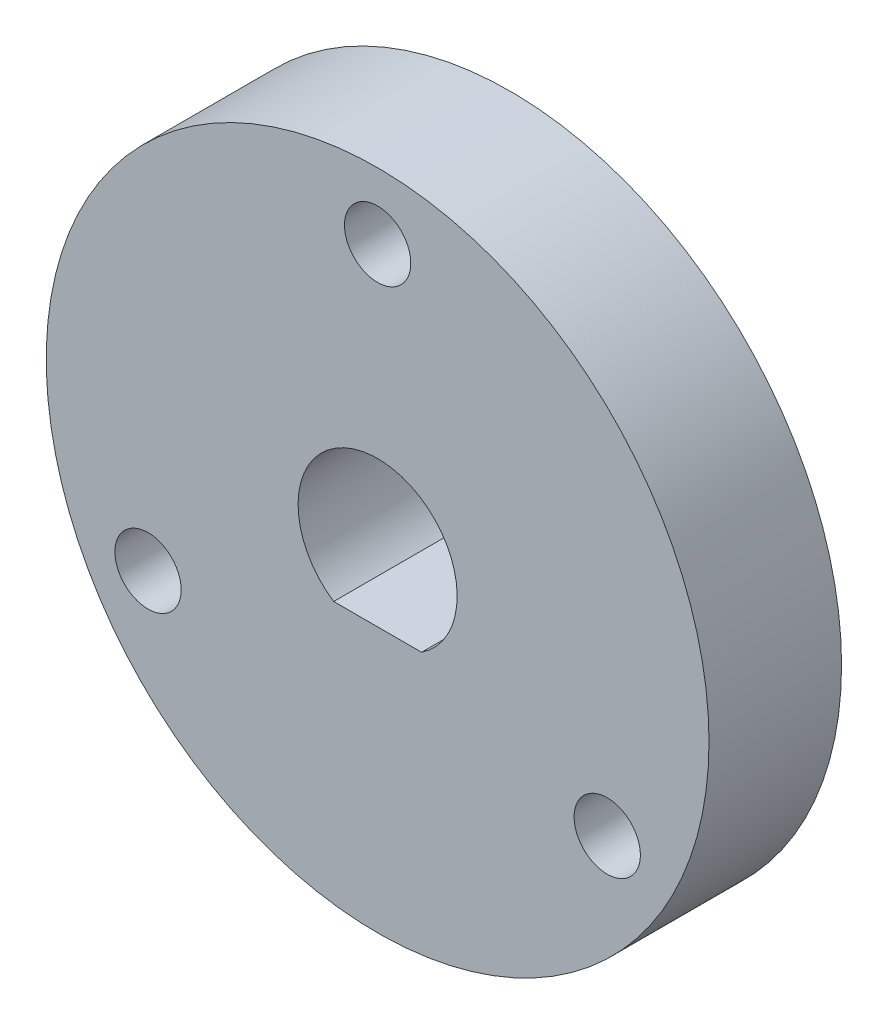
SolidWorks part; units mm, degrees
ref_plane "Front Plane" through (0, 0, 0) normal (0, 0, 1) x (1, 0, 0)
ref_plane "Top Plane" through (0, 0, 0) normal (0, 1, 0) x (1, 0, 0)
ref_plane "Right Plane" through (0, 0, 0) normal (1, 0, 0) x (0, 0, -1)
sketch "Sketch1" plane through (0, 0, 0) normal (0, 0, 1) x (1, 0, 0)
  line L0 (-3.3166, -5) -> (3.3166, -5)
  arc A0 (3.3166, -5) -> (-3.3166, -5) centre (0, 0) ccw
  circle A1 centre (0, 0) radius 25
  point P0 (0, 0)
  dimension "D1" = 50
extrude "Boss-Extrude1" add sketch "Sketch1" against normal blind 10
sketch "Sketch2" plane through (0, 0, -10) normal (0, 0, -1) x (-1, 0, 0)
  circle A0 centre (0, 20) radius 2.5
  circle A1 centre (17.3205, -10) radius 2.5
  circle A2 centre (-17.3205, -10) radius 2.5
  dimension "D2" = 5
  dimension "D1" = 20
  dimension "D3" = 3
extrude "Cut-Extrude1" cut sketch "Sketch2" against normal through all
